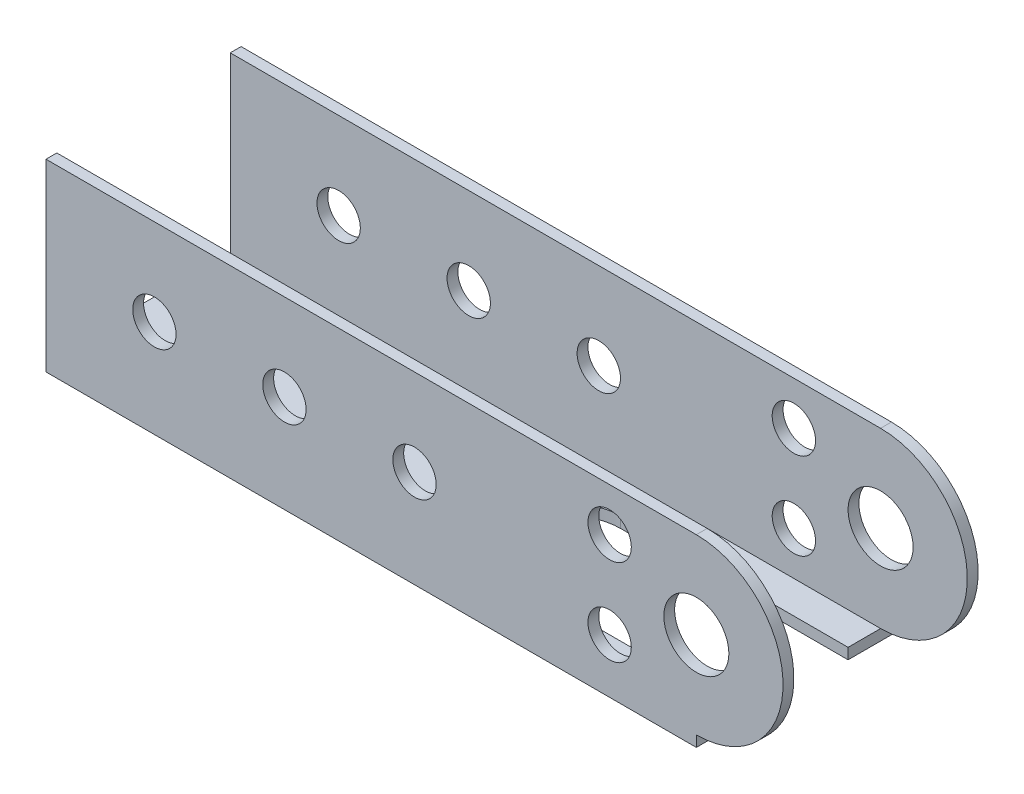
SolidWorks part; units mm, degrees
ref_plane "前视" through (0, 0, 0) normal (0, 0, 1) x (1, 0, 0)
ref_plane "上视" through (0, 0, 0) normal (0, 1, 0) x (1, 0, 0)
ref_plane "右视" through (0, 0, 0) normal (1, 0, 0) x (0, 0, -1)
sketch "草图1" plane through (0, 0, 0) normal (0, 0, 1) x (1, 0, 0)
  line L0 (-10, 12.1517) -> (-10, -12.1517) construction
  line L1 (-15, 4) -> (15, 4)
  line L2 (-15, 4) -> (-15, -4)
  line L3 (-15, -4) -> (15, -4)
  line L4 (-16.7978, 0) -> (28.1127, 0) construction
  line L5 (11, 8.6867) -> (11, -8.5755) construction
  line L7 (-4, 14.6585) -> (-4, -12.1517) construction
  line L8 (2, 14.6585) -> (2, -12.1517) construction
  arc A0 (15, -4) -> (15, 4) centre (15, 0) ccw
  circle A1 centre (15, 0) radius 1.5
  circle A2 centre (-10, 0) radius 1
  circle A3 centre (-4, 0) radius 1
  circle A4 centre (2, 0) radius 1
  circle A5 centre (11, 2) radius 1
  circle A6 centre (11, -2) radius 1
  point P0 (0, 0)
  dimension "D3" = 8
  dimension "D4" = 3
  dimension "D8" = 2
  dimension "D9" = 2
  dimension "D10" = 2
  dimension "D14" = 2
  dimension "D15" = 2
  dimension "D1" = 8
  dimension "D2" = 30
  dimension "D5" = 5
  dimension "D6" = 11
  dimension "D7" = 17
  dimension "D11" = 2
  dimension "D12" = 2
  dimension "D13" = 4
ref_plane "基准面1" through (0, 0, 8) normal (0, 0, 1) x (1, 0, 0)
sketch "草图2" plane through (0, 0, 8) normal (0, 0, 1) x (1, 0, 0)
  line L3 (15, 4) -> (-15, 4)
  line L4 (-15, -4) -> (15, -4)
  line L5 (-15, 4) -> (-15, -4)
  line L6 (15, 4) -> (-15, 4)
  line L7 (-15, -4) -> (15, -4)
  line L8 (-15, 4) -> (-15, -4)
  circle A1 centre (15, 0) radius 1.5
  circle A2 centre (15, 0) radius 1.5
  arc A3 (15, -4) -> (15, 4) centre (15, 0) ccw
  arc A4 (15, -4) -> (15, 4) centre (15, 0) ccw
  circle A5 centre (11, -2) radius 1
  circle A6 centre (11, -2) radius 1
  circle A7 centre (11, 2) radius 1
  circle A8 centre (11, 2) radius 1
  circle A9 centre (2, 0) radius 1
  circle A10 centre (2, 0) radius 1
  circle A11 centre (-4, 0) radius 1
  circle A12 centre (-4, 0) radius 1
  circle A13 centre (-10, 0) radius 1
  circle A14 centre (-10, 0) radius 1
  dimension "D1" = 0
  dimension "D2" = 0
  dimension "D3" = 0
  dimension "D4" = 0
  dimension "D5" = 0
  dimension "D6" = 0
  dimension "D7" = 0
extrude "凸台-拉伸1" add sketch "草图2" along normal blind 0.5
extrude "凸台-拉伸2" add sketch "草图1" against normal blind 0.5 separate body
ref_plane "基准面2" through (0, -4, 0) normal (0, 1, 0) x (1, 0, 0)
sketch "草图4" plane through (0, -4, 0) normal (0, 1, 0) x (1, 0, 0)
  line L0 (-15, 0.5) -> (2, 0.5)
  line L1 (-15, 0.5) -> (-15, 0) construction
  line L2 (2, 0.5) -> (2, 0) construction
  line L3 (2, -1.5) -> (2, -6.5)
  line L4 (2, -8.5) -> (2, -8) construction
  line L5 (15, -8.5) -> (-15, -8.5) construction
  line L6 (2, -8.5) -> (-15, -8.5)
  line L7 (-15, -8.5) -> (-15, 0.5)
  line L9 (2, -8.5) -> (15, -8.5)
  line L11 (2, -6.5) -> (15, -6.5)
  line L12 (15, -8.5) -> (15, -6.5)
  line L13 (2, 0.5) -> (15, 0.5)
  line L15 (2, -1.5) -> (15, -1.5)
  line L16 (15, 0.5) -> (15, -1.5)
  dimension "D1" = 2
  dimension "D2" = 2
extrude "凸台-拉伸4" add sketch "草图4" against normal blind 0.5
fillet "圆角1" radius 2.5 2 edges at (2, -4.25, 1.5) (2, -4.25, 6.5)
